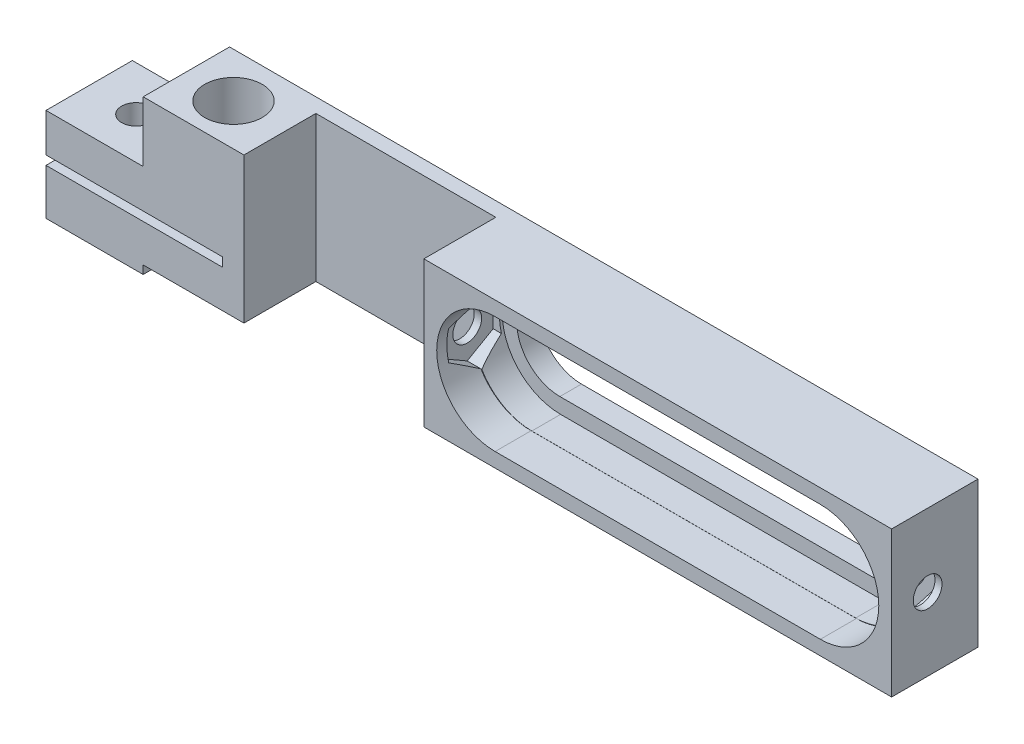
SolidWorks part; units mm, degrees
ref_plane "Plan de face" through (0, 0, 0) normal (0, 0, 1) x (1, 0, 0)
ref_plane "Plan de dessus" through (0, 0, 0) normal (0, 1, 0) x (1, 0, 0)
ref_plane "Plan de droite" through (0, 0, 0) normal (1, 0, 0) x (0, 0, -1)
sketch "Esquisse1" plane through (0, 0, 0) normal (0, 0, 1) x (1, 0, 0)
  line L0 (-15.0279, -6.6593) -> (-15.0279, 13.5742) construction
  line L1 (-47.5279, 13.5742) -> (17.4721, 13.5742)
  line L2 (-47.5279, 13.5742) -> (-47.5279, -6.6593)
  line L3 (-47.5279, -6.6593) -> (17.4721, -6.6593)
  line L4 (17.4721, 13.5742) -> (17.4721, -6.6593)
  line L5 (-37.6252, 3.4574) -> (7.5695, 3.4574) construction
  line L6 (-37.6252, 11.5742) -> (7.5695, 11.5742)
  line L7 (-37.6252, -4.6593) -> (7.5695, -4.6593)
  line L9 (-47.5279, 13.5742) -> (-72.5279, 13.5742)
  line L10 (-47.5279, 13.5742) -> (-47.5279, -6.6593)
  line L11 (-47.5279, -6.6593) -> (-72.5279, -6.6593)
  line L18 (17.4721, 13.5742) -> (17.4721, -6.6593)
  line L27 (-37.6252, 3.4574) -> (7.5695, 3.4574) construction
  line L32 (-72.5279, 13.5742) -> (-86.5279, 13.5742)
  line L33 (-72.5279, 13.5742) -> (-72.5279, -6.6593)
  line L34 (-72.5279, -6.6593) -> (-86.5279, -6.6593)
  line L35 (-86.5279, 13.5742) -> (-86.5279, -6.6593)
  line L36 (-37.6252, 9.4574) -> (7.5695, 9.4574)
  line L37 (-37.6252, -2.5426) -> (7.5695, -2.5426)
  line L57 (-72.5279, 9.0712) -> (-72.5279, 10.0712)
  line L65 (-72.5279, -1.9277) -> (-72.5279, -2.9277)
  line L66 (-86.5279, 5.1879) -> (-100.0313, 5.1879)
  line L67 (-86.5279, 5.1879) -> (-86.5279, -7.811)
  line L68 (-86.5279, -7.811) -> (-100.0313, -7.811)
  line L69 (-100.0313, 5.1879) -> (-100.0313, -7.811)
  line L70 (-86.5279, 5.1879) -> (-100.0313, 5.1879)
  line L71 (-86.5279, 5.1879) -> (-86.5279, 6.6909)
  line L72 (-86.5279, 6.6909) -> (-100.0313, 6.6909)
  line L73 (-100.0313, 5.1879) -> (-100.0313, 6.6909)
  line L74 (-100.0313, 6.6909) -> (-101.5279, 6.6909)
  line L75 (-100.0313, 6.6909) -> (-100.0313, -7.811)
  line L76 (-100.0313, -7.811) -> (-101.5279, -7.811)
  line L77 (-101.5279, 6.6909) -> (-101.5279, -7.811)
  line L78 (-101.5279, -7.811) -> (-86.5279, -7.811)
  line L79 (-101.5279, -7.811) -> (-101.5279, -9.5426)
  line L80 (-101.5279, -9.5426) -> (-86.5279, -9.5426)
  line L81 (-86.5279, -7.811) -> (-86.5279, -9.5426)
  line L82 (-100.0313, -0.1758) -> (-75.5279, -0.1758)
  line L83 (-100.0313, -0.1758) -> (-100.0313, -1.4258)
  line L84 (-100.0313, -1.4258) -> (-75.5279, -1.4258)
  line L85 (-75.5279, -0.1758) -> (-75.5279, -1.4258)
  line L86 (-47.5279, 13.5742) -> (-35.202, 13.5742)
  arc A0 (-37.6252, 11.5742) -> (-37.6252, -4.6593) centre (-37.6252, 3.4574) ccw
  arc A1 (7.5695, -4.6593) -> (7.5695, 11.5742) centre (7.5695, 3.4574) ccw
  arc A2 (-37.6252, 9.4574) -> (-37.6252, -2.5426) centre (-37.6252, 3.4574) ccw
  arc A3 (7.5695, -2.5426) -> (7.5695, 9.4574) centre (7.5695, 3.4574) ccw
  point P8 (-15.0279, 3.4574)
  point P13 (-72.5279, 3.4574)
  point P29 (-15.0279, 3.4574)
  point P43 (0, 0)
  dimension "D5" = 8.1167
  dimension "D1" = 65
  dimension "D2" = 15
  dimension "D3" = 25
  dimension "D4" = 2
  dimension "D6" = 3
  dimension "D7" = 14
  dimension "D8" = 1.25
  dimension "D9" = 20.2335
  dimension "D10" = 12
extrude "Boss.-Extru.9" add sketch "Esquisse1" along normal blind 12 contours L4 L1 L2 L3 A1 L7 A0 L6 region at (-41.3649, 12.8934, 0)
extrude "Boss.-Extru.10" add sketch "Esquisse1<14>" along normal blind 7 contours L7 A1 L6 A0 A3 L37 A2 L36 region at (-15.0279, 10.9388, 0)
sketch "Esquisse1<14>" plane through (0, 0, 0) normal (0, 0, 1) x (1, 0, 0) same geometry as "Esquisse1"
extrude "Boss.-Extru.11" add sketch "Esquisse1<17>" along normal blind 12 separate body contours L82 L85 L84 L35 L34 L33 L32 | L69 L82 L35 L66 | L84 L69 L68 L35 region at (-79.4513, 3.6747, 0) region at (-93.2796, -4.6184, 0) region at (-93.2796, 2.5061, 0)
sketch "Esquisse1<17>" plane through (0, 0, 0) normal (0, 0, 1) x (1, 0, 0) same geometry as "Esquisse1"
extrude "Boss.-Extru.12" add sketch "Esquisse1<18>" along normal blind 2 contours L9 L33 L11 L2 region at (-60.0279, 3.4574, 0)
sketch "Esquisse1<18>" plane through (0, 0, 0) normal (0, 0, 1) x (1, 0, 0) same geometry as "Esquisse1"
sketch "Esquisse3" plane through (0, 0, 0) normal (0, 1, 0) x (1, 0, 0)
  circle A0 centre (-79.7583, -6.2237) radius 4
  circle A1 centre (-93.295, -6.2237) radius 2
  dimension "D1" = 4
  dimension "D2" = 8
extrude "Enlèv. mat.-Extru.5" cut sketch "Esquisse3" against normal through all both and the other way through all
sketch "Esquisse4" plane through (0, -7.811, 0) normal (0, -1, 0) x (1, 0, 0)
  line L1 (-91.2789, 2.7211) -> (-89.2536, 6.2184)
  line L2 (-89.2536, 6.2184) -> (-91.2698, 9.721)
  line L3 (-91.2698, 9.721) -> (-95.3112, 9.7263)
  line L4 (-95.3112, 9.7263) -> (-97.3365, 6.229)
  line L5 (-97.3365, 6.229) -> (-95.3203, 2.7263)
  line L6 (-95.3203, 2.7263) -> (-91.2789, 2.7211)
  circle A0 centre (-93.295, 6.2237) radius 3.5 construction
extrude "Enlèv. mat.-Extru.6" cut sketch "Esquisse4" against normal blind 2
sketch "Esquisse5" plane through (17.4721, 0, 0) normal (1, 0, 0) x (0, 0, -1)
sketch "Esquisse9" plane through (0, 0, 12) normal (0, 0, 1) x (1, 0, 0)
  line L0 (-45.742, 3.4574) -> (15.6863, 3.4574) construction
  line L1 (-37.5279, 3.4574) -> (7.4721, 3.4574) construction
  line L2 (-37.5279, 11.5574) -> (7.4721, 11.5574)
  line L3 (-37.5279, -4.6426) -> (7.4721, -4.6426)
  arc A0 (-37.6252, 11.5742) -> (-37.6252, -4.6593) centre (-37.6252, 3.4574) ccw construction
  arc A1 (7.5695, -4.6593) -> (7.5695, 11.5742) centre (7.5695, 3.4574) ccw construction
  arc A2 (-37.5279, 11.5574) -> (-37.5279, -4.6426) centre (-37.5279, 3.4574) ccw
  arc A3 (7.4721, -4.6426) -> (7.4721, 11.5574) centre (7.4721, 3.4574) ccw
  point P10 (-15.0279, 3.4574)
extrude "Enlèv. mat.-Extru.13" cut sketch "Esquisse9" against normal blind 9
sketch "Esquisse10" plane through (0, 0, 12) normal (0, 0, 1) x (1, 0, 0)
  line L0 (-15.0279, 11.5742) -> (-15.0279, -4.6593) construction
  line L1 (-37.6252, 11.5742) -> (7.5695, 11.5742) construction
  line L2 (-37.6252, -4.6593) -> (7.5695, -4.6593) construction
  line L3 (-45.742, 3.4574) -> (15.6863, 3.4574) construction
  line L4 (7.4721, 3.4574) -> (-37.5279, 3.4574) construction
  line L5 (7.4721, -0.5426) -> (-37.5279, -0.5426)
  line L6 (7.4721, 7.4574) -> (-37.5279, 7.4574)
  arc A0 (-37.6252, 11.5742) -> (-37.6252, -4.6593) centre (-37.6252, 3.4574) ccw construction
  arc A1 (7.5695, -4.6593) -> (7.5695, 11.5742) centre (7.5695, 3.4574) ccw construction
  arc A2 (7.4721, -0.5426) -> (7.4721, 7.4574) centre (7.4721, 3.4574) ccw
  arc A3 (-37.5279, 7.4574) -> (-37.5279, -0.5426) centre (-37.5279, 3.4574) ccw
  point P16 (-15.0279, 3.4574)
sketch "Esquisse11" plane through (17.4721, 0, 0) normal (1, 0, 0) x (0, 0, -1)
  line L0 (-7, 11.5742) -> (-7, -4.6593) construction
  line L1 (-7, -0.6995) -> (-3.4, 1.379)
  line L2 (-3.4, 1.379) -> (-3.4, 5.5359)
  line L3 (-3.4, 5.5359) -> (-7, 7.6144)
  line L4 (-7, 7.6144) -> (-10.6, 5.5359)
  line L5 (-10.6, 5.5359) -> (-10.6, 1.379)
  line L6 (-10.6, 1.379) -> (-7, -0.6995)
  circle A0 centre (-7, 3.4574) radius 3.6 construction
sketch "Esquisse12" plane through (0, 0, 0) normal (1, 0, 0) x (0, 0, -1)
  circle A0 centre (-7, 3.4574) radius 2
extrude "Enlèv. mat.-Extru.15" cut sketch "Esquisse12" against normal blind 53 and the other way blind 38
sketch "Esquisse13" plane through (0, 0, 0) normal (1, 0, 0) x (0, 0, -1)
  line L1 (-7, -0.6995) -> (-3.4, 1.379)
  line L2 (-3.4, 1.379) -> (-3.4, 5.5359)
  line L3 (-3.4, 5.5359) -> (-7, 7.6144)
  line L4 (-7, 7.6144) -> (-10.6, 5.5359)
  line L5 (-10.6, 5.5359) -> (-10.6, 1.379)
  line L6 (-10.6, 1.379) -> (-7, -0.6995)
  circle A0 centre (-7, 3.4574) radius 3.6 construction
extrude "Enlèv. mat.-Extru.16" cut sketch "Esquisse13" against normal blind 46.5 and the other way blind 16.5
